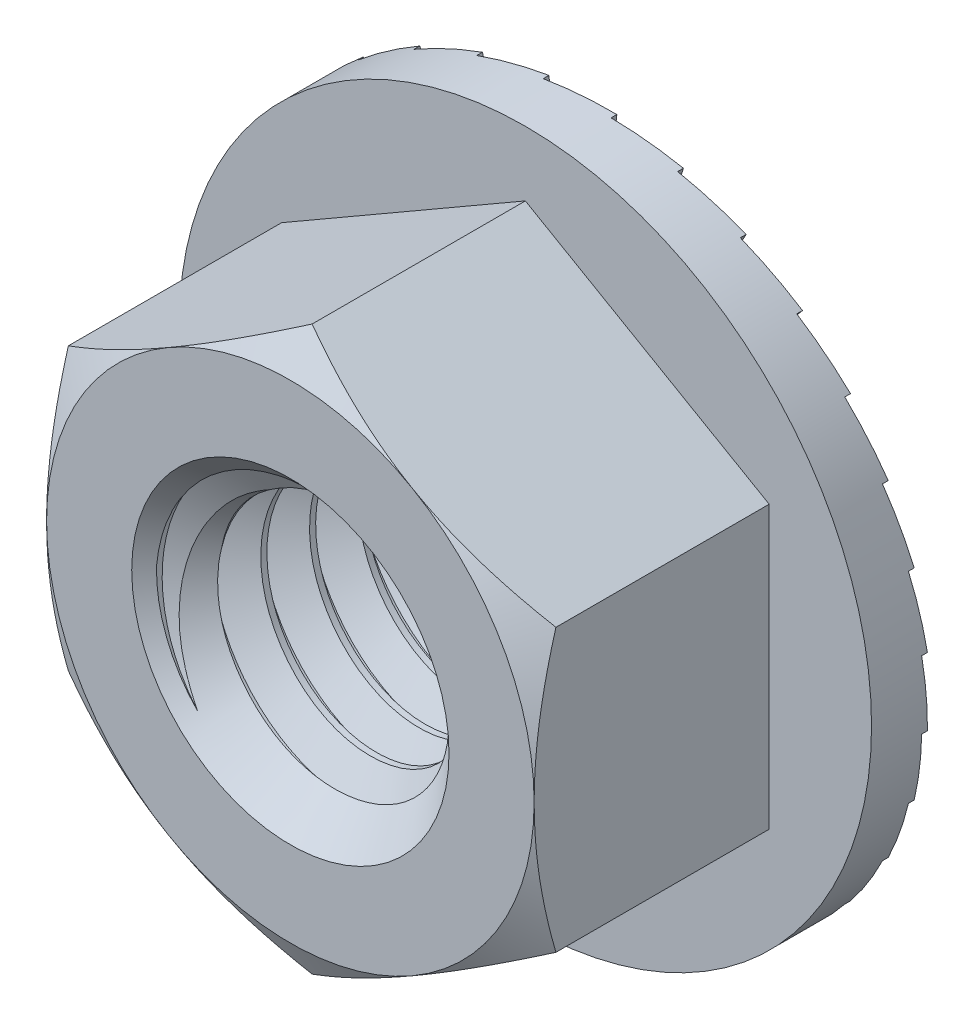
SolidWorks part; units mm, degrees
material "Plain Carbon Steel"
ref_plane "Front Plane" through (0, 0, 0) normal (0, 0, 1) x (1, 0, 0)
ref_plane "Top Plane" through (0, 0, 0) normal (0, 1, 0) x (1, 0, 0)
ref_plane "Right Plane" through (0, 0, 0) normal (1, 0, 0) x (0, 0, -1)
sketch "Sketch1" plane through (0, 0, 0) normal (0, 0, 1) x (1, 0, 0)
  line L1 (0, 5.7735) -> (-5, 2.8868)
  line L2 (-5, 2.8868) -> (-5, -2.8868)
  line L3 (-5, -2.8868) -> (0, -5.7735)
  line L4 (0, -5.7735) -> (5, -2.8868)
  line L5 (5, -2.8868) -> (5, 2.8868)
  line L6 (5, 2.8868) -> (0, 5.7735)
  circle A0 centre (0, 0) radius 5 construction
  dimension "Hex" = 10
extrude "Extrude1" add sketch "Sketch1" against normal blind 6
sketch "Sketch13" plane through (0, 0, -6) normal (0, 0, -1) x (-1, 0, 0)
  circle A0 centre (0, 0) radius 7.1
  dimension "Flange od" = 14.2
extrude "Extrude3" add sketch "Sketch13" against normal blind 1.18
sketch "Sketch2" plane through (0, 0, 0) normal (0, 0, 1) x (1, 0, 0)
  circle A0 centre (0, 0) radius 5 construction
  circle A1 centre (0, 0) radius 5
extrude "Cut-Extrude1" cut sketch "Sketch2" against normal through all draft 60 flip side to cut
sketch "Sketch4" plane through (0, 0, 0) normal (0, 0, 1) x (1, 0, 0)
  circle A0 centre (0, 0) radius 3
  dimension "Thread Dia" = 6
extrude "Cut-Extrude3" cut sketch "Sketch4" against normal through all
sketch "Sketch7" plane through (0, 0, 0) normal (0, 0, 1) x (1, 0, 0)
  circle A4 centre (0, 0) radius 3.254
  circle A5 centre (0, 0) radius 3.254
  dimension "D1" = 0.254
sketch "Sketch8" plane through (0, 0, -6) normal (0, 0, -1) x (-1, 0, 0)
  circle A1 centre (0, 0) radius 3.254
  circle A2 centre (0, 0) radius 3.254 construction
sketch "Sketch5" plane through (0, 0, 0) normal (0, 0, 1) x (1, 0, 0)
  circle A0 centre (0, 0) radius 3 construction
  circle A1 centre (0, 0) radius 3
curve "Helix/Spiral1" pitch 1 height 7 radius 3 centre (0, 0, 0) axis (0, 0, -1) start towards (0, 1, 0) parameters "pitch"=1
sketch "Sketch9" plane through (0, 0, 0) normal (1, 0, 0) x (0, 0, -1)
  line L0 (-0.5, 3) -> (-0.375, 3)
  line L1 (-0.375, 3) -> (0, 2.3505)
  line L2 (-0.5, 3) -> (-0.875, 2.3505)
  line L3 (-0.875, 2.3505) -> (0, 2.3505)
  line L4 (-0.4375, 3) -> (-0.4375, 2.3505) construction
  line L5 (-0.6875, 2.6752) -> (-0.1875, 2.6752) construction
  line L7 (0, 2.3505) -> (0, 3) construction
  line L8 (0, 3) -> (0, -3) construction
  dimension "D1" = 0.125
  dimension "D2" = 0.5
  dimension "D3" = 60
sketch "Sketch12" plane through (0, 0, 0) normal (0, 0, 1) x (1, 0, 0)
  circle A0 centre (0, 0) radius 2.3505
  circle A1 centre (0, 0) radius 3 construction
  circle A2 centre (0, 0) radius 3
extrude "Extrude2" add sketch "Sketch12" against normal up to surface (6 mm away) up to face at (3, 0, -6)
sweep "Cut-Sweep1" cut profiles "Sketch9" path "Helix/Spiral1" align with end faces yes
extrude "Cut-Extrude6" cut sketch "Sketch7" against normal through all draft 45
extrude "Cut-Extrude7" cut sketch "Sketch8" against normal through all draft 45
sketch "Sketch14" plane through (0, 0, -6) normal (0, 0, -1) x (-1, 0, 0)
  circle A4 centre (0, 0) radius 5.286
  circle A5 centre (0, 0) radius 5.286
  dimension "D1" = 2.032
extrude "Cut-Extrude8" cut sketch "Sketch14" against normal blind 0.118 flip side to cut
sketch "Sketch15" plane through (0, 0, -5.882) normal (0, 0, -1) x (-1, 0, 0)
  line L0 (-0.5181, 5.2605) -> (-0.6959, 7.0658)
  line L1 (0.5181, 5.2605) -> (0.6959, 7.0658)
  line L2 (0, 0) -> (0.5181, 5.2605) construction
  line L3 (0, 0) -> (-0.5181, 5.2605) construction
  circle A0 centre (0, 0) radius 7.1 construction
  circle A1 centre (0, 0) radius 5.286 construction
  arc A2 (0.6959, 7.0658) -> (-0.6959, 7.0658) centre (0, 0) ccw
  arc A3 (0.5181, 5.2605) -> (-0.5181, 5.2605) centre (0, 0) ccw
  dimension "D1" = 11.25
extrude "Extrude4" add sketch "Sketch15" along normal up to surface (0.118 mm away) separate body up to face at (-3.254, 0, -6)
sketch "Sketch16" plane through (0, 0, 0) normal (0, 1, 0) x (1, 0, 0)
  line L0 (-0.6959, 5.882) -> (0.6959, 6)
  line L4 (-0.6959, 5.882) -> (0.6959, 5.882)
  line L5 (0.6959, 5.882) -> (0.6959, 6)
  line L6 (0.6959, 6) -> (-0.6959, 6)
  line L7 (-0.6959, 6) -> (-0.6959, 5.882)
  line L8 (-0.6959, 5.882) -> (0.6959, 5.882) construction
  line L9 (0.6959, 5.882) -> (0.6959, 6) construction
  line L10 (0.6959, 6) -> (-0.6959, 6)
  line L11 (-0.6959, 6) -> (-0.6959, 5.882)
  dimension "D1" = 0
extrude "Cut-Extrude9" cut sketch "Sketch16" along normal through all
pattern_circular "CirPattern1" count 32 over 360 about axis through (0, 0, -8.3067) along (0, 0, 1) of bodies 119
combine bodies "Combine1" operation type add bodies to combine 117 119 120 121 122 123 124 125 126 127 128 129 130 131 132 133 134 135 136 137 139 140 141 142 143 144 145 146 147 148 149 150 151
sketch "Sketch17" plane through (0, 0, 0) normal (1, 0, 0) x (0, 0, -1)
  line L0 (6, 7.1) -> (6, -7.1) construction
  line L1 (4.82, 7.1) -> (4.82, -7.1) construction
  dimension "D1" = 1.18
sketch "Sketch18" plane through (0, 0, -4.82) normal (0, 0, 1) x (1, 0, 0)
  circle A0 centre (0, 0) radius 7.1
  circle A1 centre (0, 0) radius 7.1 construction
equation "\"D2@Sketch9\" = \"pitch@Helix/Spiral1\"*.5"
equation "\"D3@Helix/Spiral1\" = \"pitch@Helix/Spiral1\"+\"Height@Extrude1\""
equation "\"D1@Sketch9\" = \"pitch@Helix/Spiral1\"*.125"
equation "\"D1@Cut-Extrude8\" = \"flange thickness@Extrude3\"*.1"
equation "\"D1@Sketch17\" = \"flange thickness@Extrude3\""
